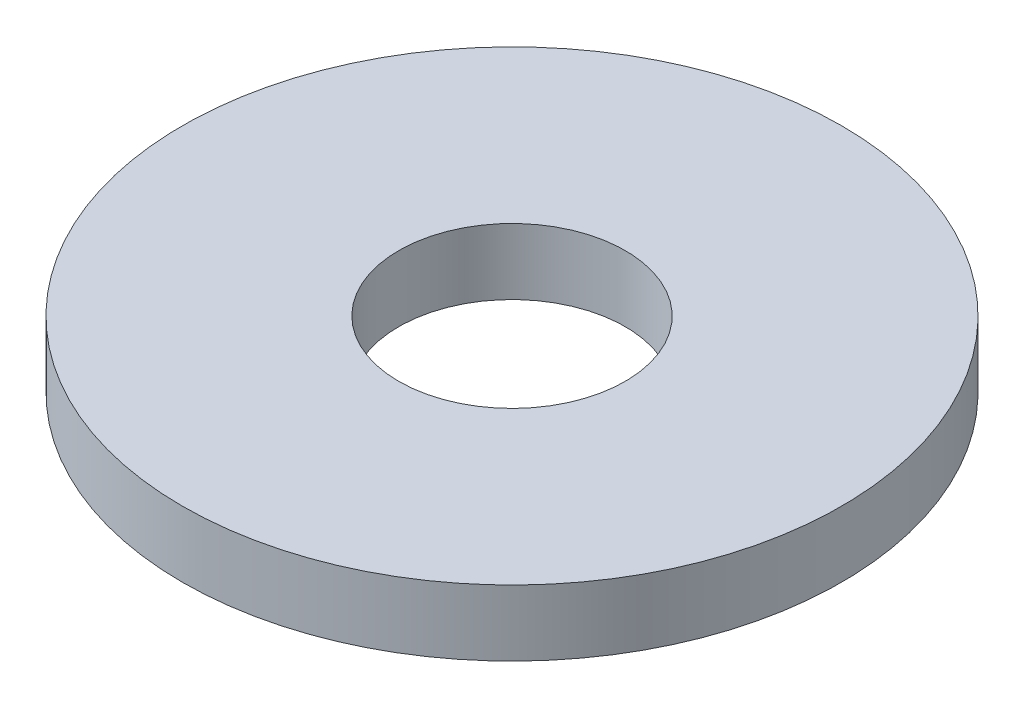
SolidWorks part; units mm, degrees
ref_plane "Front Plane" through (0, 0, 0) normal (0, 0, 1) x (1, 0, 0)
ref_plane "Top Plane" through (0, 0, 0) normal (0, 1, 0) x (1, 0, 0)
ref_plane "Right Plane" through (0, 0, 0) normal (1, 0, 0) x (0, 0, -1)
sketch "Sketch1" plane through (0, 0, 0) normal (0, 1, 0) x (1, 0, 0)
  circle A0 centre (0, 0) radius 80
  dimension "FLANGE_OD" = 160
extrude "Boss-Extrude1" add sketch "Sketch1" along normal blind 16
sketch "Sketch2" plane through (0, 0, 0) normal (0, 1, 0) x (1, 0, 0)
  circle A0 centre (0, 0) radius 27.5
  dimension "BORE_D" = 55
extrude "Cut-Extrude1" cut sketch "Sketch2" along normal through all
sketch "Sketch3" plane through (0, 16, 0) normal (0, 1, 0) x (1, 0, 0)
  circle A0 centre (0, 0) radius 17.7018 construction
  circle A1 centre (-17.7018, 0) radius 5.9281
  dimension "BOLT_D" = 11.8562
  dimension "BOLT_PCD" = 35.4037
extrude "Cut-Extrude2" cut sketch "Sketch3" against normal blind 14.7537 rebuild error yes
pattern_circular "CirPattern1" count 4 over 360 rebuild error yes
